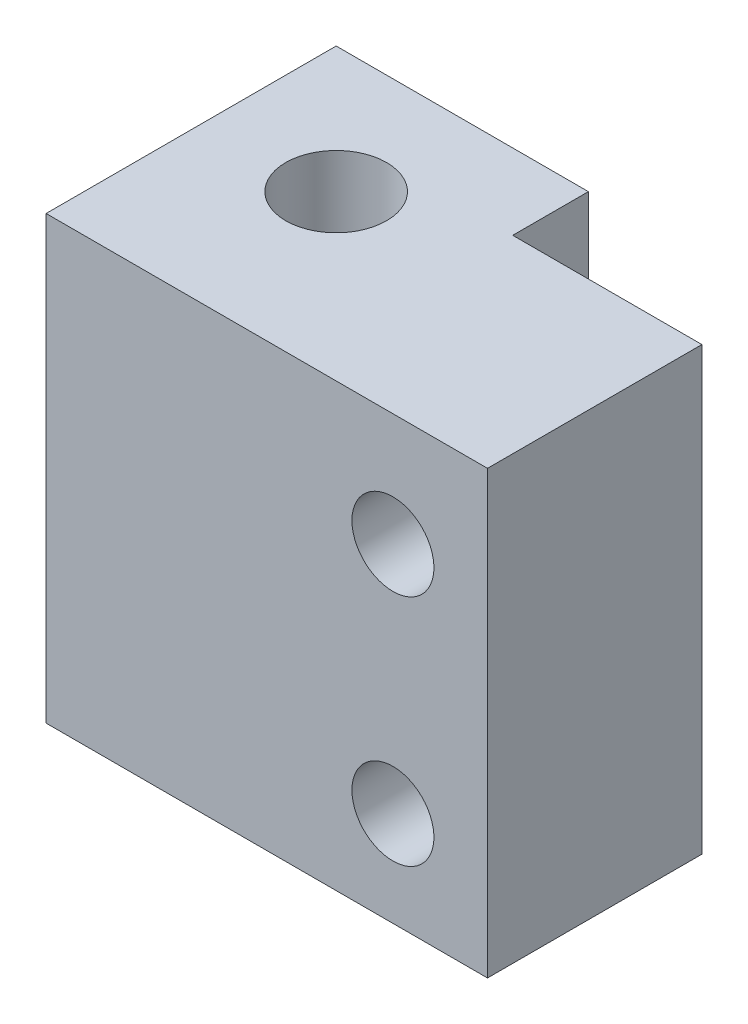
SolidWorks part; units mm, degrees
ref_plane "Front Plane" through (0, 0, 0) normal (0, 0, 1) x (1, 0, 0)
ref_plane "Top Plane" through (0, 0, 0) normal (0, 1, 0) x (1, 0, 0)
ref_plane "Right Plane" through (0, 0, 0) normal (1, 0, 0) x (0, 0, -1)
sketch "Sketch1" plane through (0, 0, 0) normal (0, 1, 0) x (1, 0, 0)
  line L5 (-10, -5.2575) -> (-10, 0.7425)
  line L6 (-10, 0.7425) -> (10, 0.7425)
  line L9 (25, -5.2575) -> (25, -22.2575)
  line L10 (0, -22.2575) -> (0, 0.7425) construction
  line L11 (-10, -5.2575) -> (-10, -22.2575)
  line L12 (10, 0.7425) -> (10, -5.2575)
  line L13 (10, -5.2575) -> (25, -5.2575)
  line L14 (-10, -22.2575) -> (25, -22.2575)
  point P2 (0, 0)
  dimension "D5" = 17
  dimension "D6" = 15
extrude "Boss-Extrude2" add sketch "Sketch1" along normal blind 35
sketch "Sketch3" plane through (0, 0, 0) normal (0, -1, 0) x (1, 0, 0)
  line L0 (0, -0.7425) -> (0, 22.2575) construction
  line L1 (10, -0.7425) -> (-10, -0.7425) construction
  circle A0 centre (0, 9.2575) radius 4
  point P8 (0, 0)
  point P9 (0, 0)
  dimension "D1" = 8
  dimension "D2" = 10
extrude "Cut-Extrude1" cut sketch "Sketch3" against normal up to next
sketch "Sketch4" plane through (0, 0, 5.2575) normal (0, 0, -1) x (-1, 0, 0)
  line L0 (-25, 17.5) -> (-10, 17.5) construction
  line L1 (-25, 35) -> (-25, 0) construction
  line L2 (-10, 35) -> (-10, 0) construction
  line L3 (-17.5, 35) -> (-17.5, 0) construction
  line L4 (-25, 35) -> (-10, 35) construction
  line L5 (-25, 0) -> (-10, 0) construction
  circle A0 centre (-17.5, 26.0458) radius 3.25
  circle A2 centre (-17.5, 7.5353) radius 3.25
  dimension "D1" = 6.5
  dimension "D2" = 6.5
extrude "Cut-Extrude2" cut sketch "Sketch4" against normal up to next
